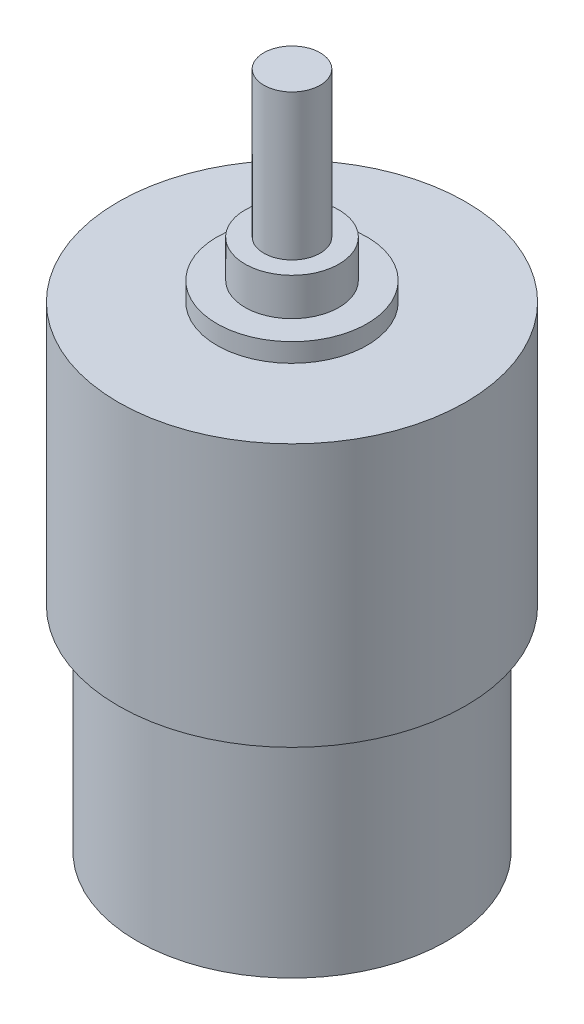
SolidWorks part; units mm, degrees
ref_plane "Front Plane" through (0, 0, 0) normal (0, 0, 1) x (1, 0, 0)
ref_plane "Top Plane" through (0, 0, 0) normal (0, 1, 0) x (1, 0, 0)
ref_plane "Right Plane" through (0, 0, 0) normal (1, 0, 0) x (0, 0, -1)
sketch "Sketch1" plane through (0, 0, 0) normal (0, 0, 1) x (1, 0, 0)
  line L0 (0, 0) -> (16.5, 0)
  line L1 (16.5, 0) -> (16.5, 22.7)
  line L2 (16.5, 22.7) -> (18.5, 22.7)
  line L3 (18.5, 22.7) -> (18.5, 50.7)
  line L4 (18.5, 50.7) -> (8, 50.7)
  line L5 (8, 50.7) -> (8, 52.7)
  line L6 (8, 52.7) -> (5, 52.7)
  line L7 (5, 52.7) -> (5, 56.7)
  line L9 (0, 72.2) -> (0, 0)
  line L10 (5, 56.7) -> (3, 56.7)
  line L11 (3, 56.7) -> (3, 72.2)
  line L12 (0, 72.2) -> (3, 72.2)
  dimension "D1" = 16.5
  dimension "D2" = 22.7
  dimension "D3" = 28
  dimension "D4" = 8
  dimension "D5" = 5
  dimension "D6" = 3
  dimension "D7" = 15.5
  dimension "D8" = 2
  dimension "D9" = 4
  dimension "D10" = 18.5
ref_axis "Axis1" through (0, 81.06, 0) along (0, -1, 0)
revolve "Revolve1" add sketch "Sketch1" angle 360 about L9
